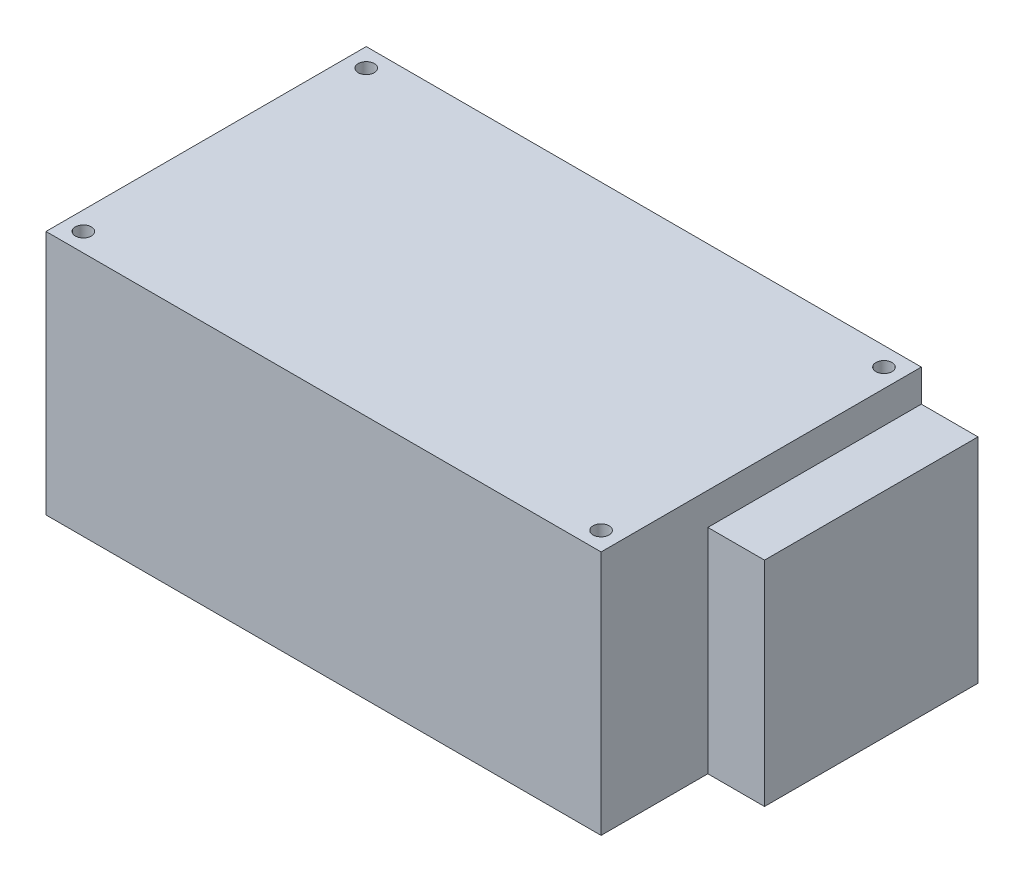
SolidWorks part; units mm, degrees
ref_plane "Front Plane" through (0, 0, 0) normal (0, 0, 1) x (1, 0, 0)
ref_plane "Top Plane" through (0, 0, 0) normal (0, 1, 0) x (1, 0, 0)
ref_plane "Right Plane" through (0, 0, 0) normal (1, 0, 0) x (0, 0, -1)
sketch "Sketch1" plane through (0, 0, 0) normal (0, 1, 0) x (1, 0, 0)
  line L1 (0, 0) -> (104, 0)
  line L2 (0, 0) -> (0, 60)
  line L3 (0, 60) -> (104, 60)
  line L4 (104, 0) -> (104, 60)
  dimension "D1" = 60
  dimension "D2" = 104
extrude "Boss-Extrude1" add sketch "Sketch1" along normal blind 46
sketch "Sketch2" plane through (0, 46, 0) normal (0, 1, 0) x (1, 0, 0)
  line L0 (0, 60) -> (104, 0) construction
  line L2 (100.5, 56.5) -> (3.5, 56.5) construction
  line L3 (100.5, 56.5) -> (100.5, 3.5) construction
  line L4 (100.5, 3.5) -> (3.5, 3.5) construction
  line L5 (3.5, 56.5) -> (3.5, 3.5) construction
  line L6 (100.5, 56.5) -> (3.5, 3.5) construction
  line L7 (100.5, 3.5) -> (3.5, 56.5) construction
  circle A0 centre (3.5, 56.5) radius 1.5
  circle A1 centre (100.5, 56.5) radius 1.5
  circle A2 centre (100.5, 3.5) radius 1.5
  circle A3 centre (3.5, 3.5) radius 1.5
  point P4 (52, 30)
  dimension "D1" = 97
  dimension "D3" = 3
  dimension "D2" = 53
sketch "Sketch3" plane through (104, 0, 0) normal (1, 0, 0) x (0, 0, -1)
  line L0 (0, 0) -> (60, 0) construction
  line L1 (20, 0) -> (60, 0)
  line L2 (20, 0) -> (20, 39.9796)
  line L3 (20, 39.9796) -> (60, 39.9796)
  line L4 (60, 0) -> (60, 39.9796)
  line L5 (60, 46) -> (60, 0) construction
  dimension "D1" = 39.9796
  dimension "D2" = 40
extrude "Cut-Extrude1" cut sketch "Sketch2" against normal through all
extrude "Boss-Extrude2" add sketch "Sketch3" along normal blind 10.6172
